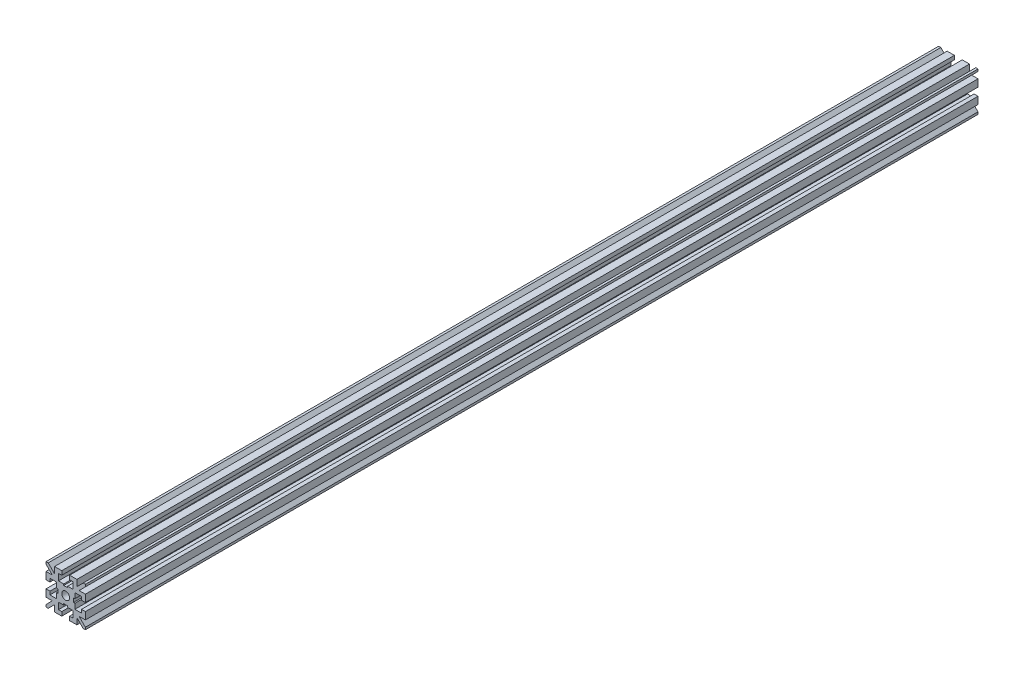
SolidWorks part; units mm, degrees
ref_plane "Front Plane" through (0, 0, 0) normal (0, 0, 1) x (1, 0, 0)
ref_plane "Top Plane" through (0, 0, 0) normal (0, 1, 0) x (1, 0, 0)
ref_plane "Right Plane" through (0, 0, 0) normal (1, 0, 0) x (0, 0, -1)
sketch "Sketch1" plane through (0, 0, 0) normal (0, 0, 1) x (1, 0, 0)
  line L1 (-9.0006, 3.7616) -> (5.9994, 3.7616)
  line L2 (-9.0006, 3.7616) -> (-9.0006, -11.2384)
  line L3 (-9.0006, -11.2384) -> (5.9994, -11.2384)
  line L4 (5.9994, 3.7616) -> (5.9994, -11.2384)
  dimension "D1" = 15
  dimension "D2" = 15
extrude "Boss-Extrude1" add sketch "Sketch1" along normal blind 340
sketch "Sketch2" plane through (0, 0, 340) normal (0, 0, 1) x (1, 0, 0)
  line L0 (-9.0006, 3.7616) -> (5.9994, -11.2384) construction
  line L1 (5.9994, 3.7616) -> (-9.0006, -11.2384) construction
  line L4 (1.9994, -4.4884) -> (1.9994, -6.4884)
  line L5 (5.9994, -3.7384) -> (1.9994, -3.7384) construction
  line L6 (5.9994, -11.2384) -> (5.9994, 3.7616) construction
  line L7 (-1.5006, 3.7616) -> (-1.5006, -3.7384) construction
  line L8 (5.9994, 3.7616) -> (-9.0006, 3.7616) construction
  line L9 (-9.0006, -3.7384) -> (-1.5006, -3.7384) construction
  line L10 (-9.0006, 3.7616) -> (-9.0006, -11.2384) construction
  line L11 (-1.5006, -11.2384) -> (-1.5006, -3.7384) construction
  line L12 (-9.0006, -11.2384) -> (5.9994, -11.2384) construction
  line L13 (1.9994, -4.4884) -> (1.4994, -4.4884)
  line L14 (1.9994, -0.9884) -> (4.4994, -0.9884)
  line L15 (1.9994, -0.9884) -> (1.9994, -2.9884)
  line L16 (1.9994, -6.4884) -> (4.4994, -6.4884)
  line L17 (4.4994, -0.9884) -> (4.4994, -6.4884)
  line L18 (-4.2506, -7.2384) -> (-4.2506, -9.7384)
  line L19 (1.9994, -2.9884) -> (1.4994, -2.9884)
  line L20 (1.4994, -4.4884) -> (1.4994, -2.9884)
  line L21 (1.4994, -3.7384) -> (-0.0006, -3.7384) construction
  line L22 (-2.2506, -7.2384) -> (-4.2506, -7.2384)
  line L23 (-2.2506, -7.2384) -> (-2.2506, -6.7384)
  line L24 (-2.2506, -6.7384) -> (-0.7506, -6.7384)
  line L25 (-0.7506, -7.2384) -> (-0.7506, -6.7384)
  line L26 (1.2494, -7.2384) -> (-0.7506, -7.2384)
  line L27 (1.2494, -7.2384) -> (1.2494, -9.7384)
  line L28 (1.2494, -9.7384) -> (-4.2506, -9.7384)
  line L29 (-5.0006, -0.9884) -> (-7.5006, -0.9884)
  line L30 (-5.0006, -2.9884) -> (-5.0006, -0.9884)
  line L31 (-5.0006, -2.9884) -> (-4.5006, -2.9884)
  line L32 (-4.5006, -2.9884) -> (-4.5006, -4.4884)
  line L33 (-5.0006, -4.4884) -> (-4.5006, -4.4884)
  line L34 (-5.0006, -6.4884) -> (-5.0006, -4.4884)
  line L35 (-5.0006, -6.4884) -> (-7.5006, -6.4884)
  line L36 (-7.5006, -6.4884) -> (-7.5006, -0.9884)
  line L37 (1.2494, -0.2384) -> (1.2494, 2.2616)
  line L38 (-0.7506, -0.2384) -> (1.2494, -0.2384)
  line L39 (-0.7506, -0.2384) -> (-0.7506, -0.7384)
  line L40 (-0.7506, -0.7384) -> (-2.2506, -0.7384)
  line L41 (-2.2506, -0.2384) -> (-2.2506, -0.7384)
  line L42 (-4.2506, -0.2384) -> (-2.2506, -0.2384)
  line L43 (-4.2506, -0.2384) -> (-4.2506, 2.2616)
  line L44 (-4.2506, 2.2616) -> (1.2494, 2.2616)
  circle A0 centre (-1.5006, -3.7384) radius 1.5
  point P60 (-1.5006, -3.7384)
  dimension "D1" = 5.5
  dimension "D2" = 2.5
  dimension "D3" = 1.5
  dimension "D4" = 2.75
  dimension "D5" = 0.5
  dimension "D6" = 1.5
  dimension "D7" = 0.75
  dimension "D8" = 4
extrude "Cut-Extrude1" cut sketch "Sketch2" against normal up to surface (340 mm away) up to face at (-1.5006, -3.7384, 0)
sketch "Sketch3" plane through (0, 0, 340) normal (0, 0, 1) x (1, 0, 0)
  line L0 (5.9994, 3.7616) -> (-9.0006, -11.2384) construction
  line L1 (-9.0006, 3.7616) -> (5.9994, -11.2384) construction
  line L2 (5.1509, 3.7616) -> (2.7494, 1.3602)
  line L3 (5.9994, 3.7616) -> (-9.0006, 3.7616) construction
  line L4 (2.7494, 1.3602) -> (2.7494, 3.7616)
  line L5 (2.7494, 3.7616) -> (5.1509, 3.7616)
  line L6 (1.2494, -0.2384) -> (1.2494, 2.2616) construction
  line L7 (5.9994, 0.5116) -> (5.9994, 2.9131)
  line L8 (3.5979, 0.5116) -> (5.9994, 0.5116)
  line L9 (5.9994, 2.9131) -> (3.5979, 0.5116)
  line L10 (1.2494, 2.2616) -> (-4.2506, 2.2616) construction
  line L11 (-3.0006, 3.7616) -> (-0.0006, 3.7616)
  line L12 (-3.0006, 3.7616) -> (-3.0006, 2.2616)
  line L13 (-3.0006, 2.2616) -> (-0.0006, 2.2616)
  line L14 (-0.0006, 3.7616) -> (-0.0006, 2.2616)
  line L15 (-2.2506, -0.7384) -> (-0.7506, -0.7384) construction
  line L16 (2.7494, -8.8369) -> (2.7494, -11.2384)
  line L17 (2.7494, -11.2384) -> (5.1509, -11.2384)
  line L18 (5.1509, -11.2384) -> (2.7494, -8.8369)
  line L19 (5.9994, -10.3898) -> (3.5979, -7.9884)
  line L20 (3.5979, -7.9884) -> (5.9994, -7.9884)
  line L21 (5.9994, -7.9884) -> (5.9994, -10.3898)
  line L22 (5.9994, -5.2384) -> (4.4994, -5.2384)
  line L23 (5.9994, -2.2384) -> (5.9994, -5.2384)
  line L24 (5.9994, -2.2384) -> (4.4994, -2.2384)
  line L25 (4.4994, -2.2384) -> (4.4994, -5.2384)
  line L26 (-6.5991, -7.9884) -> (-9.0006, -7.9884)
  line L27 (-9.0006, -7.9884) -> (-9.0006, -10.3898)
  line L28 (-9.0006, -10.3898) -> (-6.5991, -7.9884)
  line L29 (-8.1521, -11.2384) -> (-5.7506, -8.8369)
  line L30 (-5.7506, -8.8369) -> (-5.7506, -11.2384)
  line L31 (-5.7506, -11.2384) -> (-8.1521, -11.2384)
  line L32 (-3.0006, -11.2384) -> (-3.0006, -9.7384)
  line L33 (-0.0006, -11.2384) -> (-3.0006, -11.2384)
  line L34 (-0.0006, -11.2384) -> (-0.0006, -9.7384)
  line L35 (-0.0006, -9.7384) -> (-3.0006, -9.7384)
  line L36 (-5.7506, 1.3602) -> (-5.7506, 3.7616)
  line L37 (-5.7506, 3.7616) -> (-8.1521, 3.7616)
  line L38 (-8.1521, 3.7616) -> (-5.7506, 1.3602)
  line L39 (-9.0006, 2.9131) -> (-6.5991, 0.5116)
  line L40 (-6.5991, 0.5116) -> (-9.0006, 0.5116)
  line L41 (-9.0006, 0.5116) -> (-9.0006, 2.9131)
  line L42 (-9.0006, -2.2384) -> (-7.5006, -2.2384)
  line L43 (-9.0006, -5.2384) -> (-9.0006, -2.2384)
  line L44 (-9.0006, -5.2384) -> (-7.5006, -5.2384)
  line L45 (-7.5006, -5.2384) -> (-7.5006, -2.2384)
  point P24 (-1.5006, -0.7384)
  point P27 (-1.5006, -3.7384)
  point P61 (-1.5006, -3.7384)
  dimension "D1" = 0.6
  dimension "D2" = 1.5
  dimension "D3" = 3
  dimension "D4" = 1.5
  dimension "D5" = 4
extrude "Cut-Extrude2" cut sketch "Sketch3" against normal up to surface (340 mm away) up to face at (-1.5006, 0.2616, 0)
